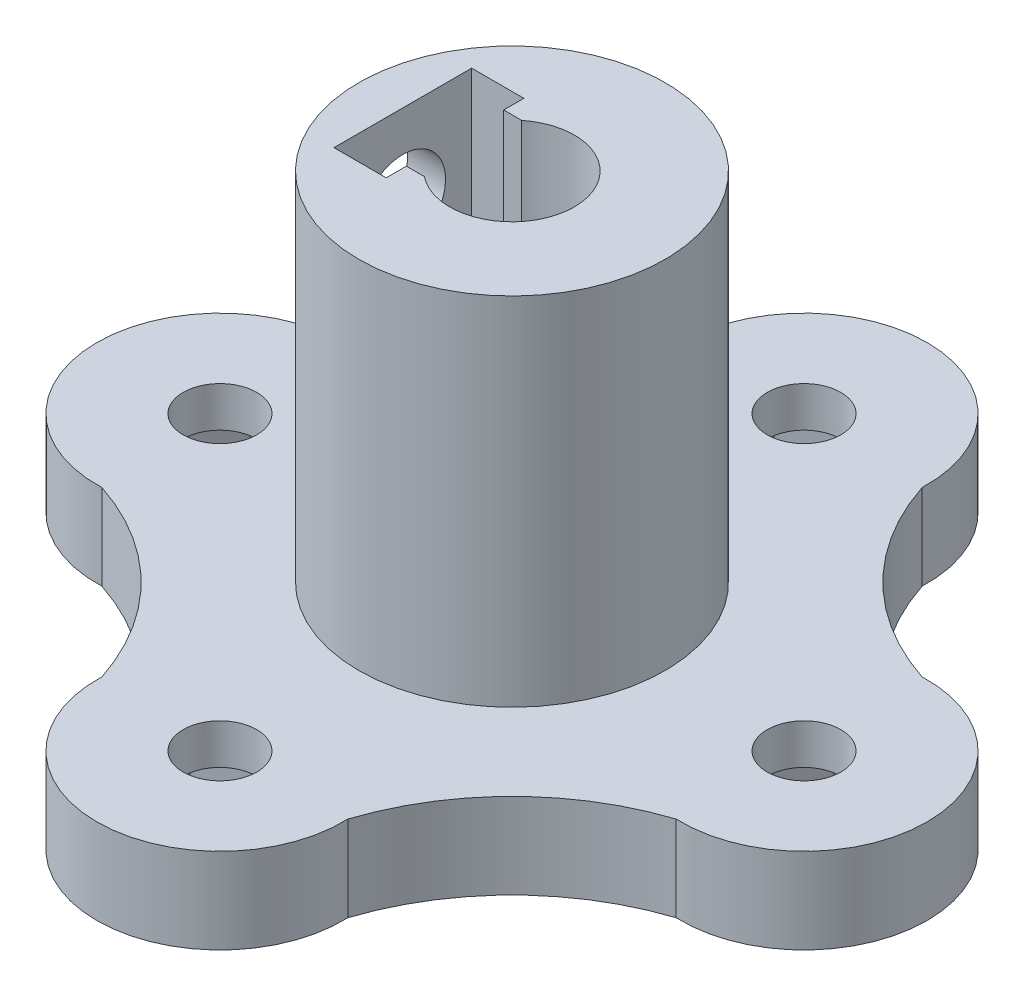
SolidWorks part; units mm, degrees
material "ABS"
ref_plane "Front Plane" through (0, 0, 0) normal (0, 0, 1) x (1, 0, 0)
ref_plane "Top Plane" through (0, 0, 0) normal (0, 1, 0) x (1, 0, 0)
ref_plane "Right Plane" through (0, 0, 0) normal (1, 0, 0) x (0, 0, -1)
sketch "Sketch1" plane through (0, 0, 0) normal (0, 1, 0) x (1, 0, 0)
  circle A0 centre (0, 0) radius 15.25
  circle A1 centre (0, 0) radius 2.625
  circle A2 centre (0, 12.3) radius 1.55
  circle A3 centre (12.3, 0) radius 1.55
  circle A4 centre (0, -12.3) radius 1.55
  circle A5 centre (-12.3, 0) radius 1.55
  point P15 (0, 0)
  dimension "D1" = 30.5
  dimension "D2" = 5.25
  dimension "D3" = 3.1
  dimension "D4" = 12.3
  dimension "D5" = 0
  dimension "D6" = 4
extrude "Boss-Extrude1" add sketch "Sketch1" along normal blind 3.6
sketch "Sketch2" plane through (0, 3.6, 0) normal (0, 1, 0) x (1, 0, 0)
  circle A0 centre (0, 0) radius 6.45
  circle A1 centre (0, 0) radius 2.625
  dimension "D1" = 12.9
  dimension "D2" = 5.25
extrude "Boss-Extrude2" add sketch "Sketch2" along normal blind 15
sketch "Sketch4" plane through (0, 18.6, 0) normal (0, 1, 0) x (1, 0, 0)
  line L0 (-4.6, 2.9) -> (-2.4, 2.9)
  line L1 (-4.6, 2.9) -> (-4.6, -2.9)
  line L2 (-4.6, -2.9) -> (-2.4, -2.9)
  line L3 (-2.4, 2.9) -> (-2.4, -2.9)
  line L4 (0, 0) -> (-2.4, 0) construction
  dimension "D1" = 2.2
  dimension "D2" = 5.8
  dimension "D4" = 2.4
extrude "Cut-Extrude4" cut sketch "Sketch4" against normal blind 7
sketch "Sketch5" plane through (0, 3.6, 0) normal (0, 1, 0) x (1, 0, 0)
  circle A0 centre (0, 12.3) radius 5.185
  circle A1 centre (12.3, 0) radius 5.185
  circle A2 centre (0, -12.3) radius 5.185
  circle A3 centre (-12.3, 0) radius 5.185
  circle A4 centre (0, 0) radius 15.25 construction
  circle A5 centre (0, 12.3) radius 1.55
  circle A6 centre (0, 12.3) radius 1.55 construction
  circle A7 centre (12.3, 0) radius 1.55
  circle A8 centre (0, -12.3) radius 1.55
  circle A9 centre (-12.3, 0) radius 1.55
  point P12 (0, 0)
  point P24 (0, 0)
  dimension "D1" = 10.37
  dimension "D2" = 4
  dimension "D3" = 4
extrude "Boss-Extrude3" add sketch "Sketch5" against normal up to surface (3.6 mm away) up to face at (0, 0, 15.25)
sketch "Sketch6" plane through (0, 3.6, 0) normal (0, 1, 0) x (1, 0, 0)
  arc A0 (4.69, 14.5109) -> (14.5109, 4.69) centre (15.4385, 15.4385) ccw
  arc A1 (4.69, 14.5109) -> (-4.69, 14.5109) centre (0, 12.3) ccw construction
  circle A2 centre (0, 0) radius 15.25 construction
  arc A3 (4.69, 14.5109) -> (14.5109, 4.69) centre (0, 0) cw
extrude "Cut-Extrude5" cut sketch "Sketch6" against normal up to next
pattern_circular "CirPattern1" count 4 over 360 about axis through (0, 3.6, 0) along (0, -1, 0) of "Cut-Extrude5"
sketch "Sketch7" plane through (0, 3.6, 0) normal (0, 1, 0) x (1, 0, 0)
  circle A0 centre (0, -12.3) radius 5.185
  circle A1 centre (0, -12.3) radius 1.55
  arc A2 (-4.69, -14.5109) -> (4.69, -14.5109) centre (0, -12.3) ccw construction
  circle A3 centre (0, -12.3) radius 1.55 construction
  circle A4 centre (-12.3, 0) radius 5.185
  circle A5 centre (-12.3, 0) radius 1.55
  circle A6 centre (0, 12.3) radius 5.185
  circle A7 centre (0, 12.3) radius 1.55
  circle A8 centre (12.3, 0) radius 5.185
  circle A9 centre (12.3, 0) radius 1.55
  circle A10 centre (0, 0) radius 6.45 construction
  point P24 (0, 0)
  dimension "D1" = 4
extrude "Boss-Extrude4" add sketch "Sketch7" against normal up to surface (3.6 mm away) up to face at (0, 0, 0)
sketch "Sketch8" plane through (0, 0, 0) normal (0, -1, 0) x (1, 0, 0)
  line L0 (0, 0) -> (0, -8.8359) construction
  line L1 (0, -8.8359) -> (-3, -10.5679)
  line L2 (-3, -10.5679) -> (-3, -14.0321)
  line L3 (-3, -14.0321) -> (0, -15.7641)
  line L4 (0, -15.7641) -> (3, -14.0321)
  line L5 (3, -14.0321) -> (3, -10.5679)
  line L6 (3, -10.5679) -> (0, -8.8359)
  line L7 (-8.8359, 0) -> (-10.5679, 3)
  line L8 (-10.5679, 3) -> (-14.0321, 3)
  line L9 (-14.0321, 3) -> (-15.7641, 0)
  line L10 (-15.7641, 0) -> (-14.0321, -3)
  line L11 (-14.0321, -3) -> (-10.5679, -3)
  line L12 (-10.5679, -3) -> (-8.8359, 0)
  line L13 (0, 8.8359) -> (3, 10.5679)
  line L14 (3, 10.5679) -> (3, 14.0321)
  line L15 (3, 14.0321) -> (0, 15.7641)
  line L16 (0, 15.7641) -> (-3, 14.0321)
  line L17 (-3, 14.0321) -> (-3, 10.5679)
  line L18 (-3, 10.5679) -> (0, 8.8359)
  line L19 (8.8359, 0) -> (10.5679, -3)
  line L20 (10.5679, -3) -> (14.0321, -3)
  line L21 (14.0321, -3) -> (15.7641, 0)
  line L22 (15.7641, 0) -> (14.0321, 3)
  line L23 (14.0321, 3) -> (10.5679, 3)
  line L24 (10.5679, 3) -> (8.8359, 0)
  circle A0 centre (0, -12.3) radius 3 construction
  circle A1 centre (0, -12.3) radius 1.55 construction
  circle A2 centre (-12.3, 0) radius 3 construction
  circle A3 centre (0, 12.3) radius 3 construction
  circle A4 centre (12.3, 0) radius 3 construction
  circle A5 centre (0, 0) radius 2.625 construction
  point P39 (0, 0)
  dimension "D1" = 6
  dimension "D2" = 4
extrude "Cut-Extrude6" cut sketch "Sketch8" against normal blind 1.9
sketch "Sketch9" plane through (0, 18.6, 0) normal (0, 1, 0) x (1, 0, 0)
  line L0 (-4.6, 2.9) -> (-4.6, -2.9) construction
  line L1 (-4.6, 2.05) -> (0, 2.05)
  line L2 (-4.6, 2.05) -> (-4.6, -2.05)
  line L3 (-4.6, -2.05) -> (0, -2.05)
  line L4 (0, 2.05) -> (0, -2.05)
  arc A0 (-2.4, -1.0633) -> (-2.4, 1.0633) centre (0, 0) ccw construction
  point P6 (0, 0)
  point P11 (0, 0)
  dimension "D1" = 4.1
extrude "Cut-Extrude7" cut sketch "Sketch9" against normal up to surface (7 mm away) up to face at (-3.1708, 11.6, 0)
ref_plane "Plane1" through (-6.45, 0, 0) normal (-1, 0, 0) x (0, 0, 1)
sketch "Sketch10" plane through (-6.45, 0, 0) normal (-1, 0, 0) x (0, 0, 1)
  line L0 (0, 18.6) -> (0, 3.6) construction
  line L1 (6.45, 18.6) -> (-6.45, 18.6) construction
  line L2 (12.0957, 3.6) -> (5.181, 3.6) construction
  point P0 (0, 15.1)
  dimension "D1" = 3.5
hole_wizard "M3 Clearance Hole1" positions "Sketch11" profile "Sketch12" hole size "M3" standard "ANSI Metric"
sketch "Sketch11" plane through (-6.45, 0, 0) normal (-1, 0, 0) x (0, 0, 1)
  point P0 (0, 15.1)
sketch "Sketch12" plane through (-6.45, 15.1, 0) normal (0, 1, 0) x (0, 0, 1)
  line L0 (0, 0) -> (0, 6.0815)
  line L1 (0, 6.0815) -> (1.8, 5)
  line L2 (1.8, 5) -> (1.8, 0)
  line L5 (1.8, 0) -> (0, 0)
  line L10 (0, 6.0815) -> (-1.8, 5) construction
  line L11 (0, -6.35) -> (0, 107.95) construction
  dimension "Hole Dia." = 3.6
  dimension "Hole Depth" = 5
  dimension "Drill Angle" = 118
equation "\"base_diameter\"=30.5"
equation "\"D1@Sketch1\"=\"base_diameter\""
